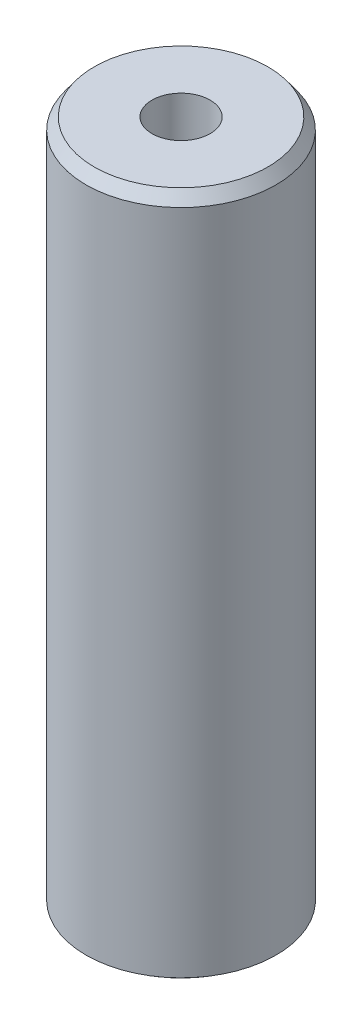
SolidWorks part; units mm, degrees
ref_plane "Front Plane" through (0, 0, 0) normal (0, 0, 1) x (1, 0, 0)
ref_plane "Top Plane" through (0, 0, 0) normal (0, 1, 0) x (1, 0, 0)
ref_plane "Right Plane" through (0, 0, 0) normal (1, 0, 0) x (0, 0, -1)
sketch "Sketch1" plane through (0, 0, 0) normal (0, 1, 0) x (1, 0, 0)
  circle A0 centre (0, 0) radius 40
  dimension "SHAFT_OD" = 80
extrude "Boss-Extrude1" add sketch "Sketch1" along normal blind 289.0182
sketch "Sketch2" plane through (0, 0, 0) normal (0, 1, 0) x (1, 0, 0)
  circle A0 centre (0, 0) radius 12.2432
  dimension "BORE_D" = 24.4865
extrude "Cut-Extrude1" cut sketch "Sketch2" along normal through all
chamfer "Chamfer1" distance 4.7884 angle 35.78 2 edges at (0, 289.0182, 40) (0, 0, 40) first distance on face at (0, 289.0182, 40) first distance on face at (0, 0, 12.2432)
